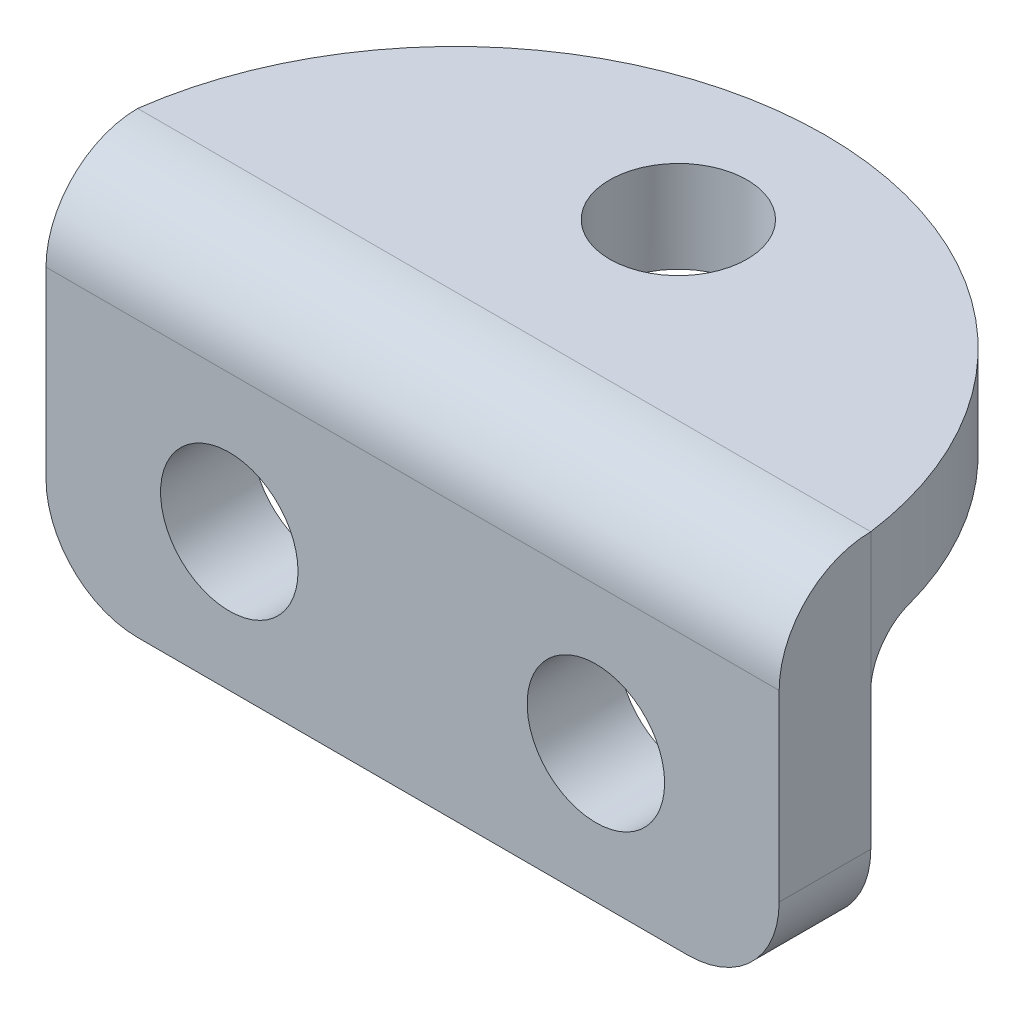
SolidWorks part; units mm, degrees
ref_plane "Front Plane" through (0, 0, 0) normal (0, 0, 1) x (1, 0, 0)
ref_plane "Top Plane" through (0, 0, 0) normal (0, 1, 0) x (1, 0, 0)
ref_plane "Right Plane" through (0, 0, 0) normal (1, 0, 0) x (0, 0, -1)
sketch "Sketch14" plane through (0, 0, 0) normal (1, 0, 0) x (0, 0, -1)
  line L0 (9.4803, -6.1219) -> (9.4803, 1.8781)
  line L1 (9.4803, 1.8781) -> (18.4803, 1.8781)
  line L2 (18.4803, 1.8781) -> (18.4803, -0.1219)
  line L3 (18.4803, -0.1219) -> (11.4803, -0.1219)
  line L4 (11.4803, -0.1219) -> (11.4803, -6.1219)
  line L5 (11.4803, -6.1219) -> (9.4803, -6.1219)
  line L9 (0, -6) -> (0, -4) construction
  line L10 (-2, -4) -> (-2, -6) construction
  line L11 (-2, -6) -> (0, -6) construction
  line L12 (0, -4) -> (0, 2) construction
  line L13 (-2, 0) -> (-2, -4) construction
  line L14 (0, 0) -> (7.0975, 0) construction
  line L15 (0, 0) -> (0, 2) construction
  line L16 (7.0975, 2) -> (0, 2) construction
  line L17 (0, 2) -> (0, 0) construction
  line L18 (0, -6) -> (0, -4)
  line L19 (-2, -4) -> (-2, -6)
  line L20 (-2, -6) -> (0, -6)
  line L21 (0, -4) -> (0, 2)
  line L22 (-2, 0) -> (-2, -4)
  line L23 (0, 0) -> (7.0975, 0)
  line L24 (0, 0) -> (0, 2)
  line L25 (7.0975, 2) -> (0, 2)
  line L26 (0, 2) -> (0, 0)
  arc A0 (0, 2) -> (-2, 0) centre (0, 0) ccw construction
  arc A1 (0, 2) -> (-2, 0) centre (0, 0) ccw
  dimension "D1" = 2
  dimension "D2" = 2
  dimension "D3" = 9
  dimension "D4" = 8
extrude "Boss-Extrude4" add sketch "Sketch14" along normal blind 16 separate body contours L5 L4 L3 L2 L1 L0 region at (0, -2.1219, -9.6007)
sketch "Sketch15" plane through (0, -0.1219, 0) normal (0, -1, 0) x (1, 0, 0)
  line L3 (8, -9.4803) -> (8, -18.4803) construction
  line L4 (16, -9.4803) -> (0, -9.4803) construction
  line L5 (16, -11.4803) -> (0, -11.4803) construction
  line L6 (16, -18.4803) -> (0, -18.4803) construction
  line L11 (0, -11.4803) -> (0, -18.4803)
  line L12 (0, -18.4803) -> (16, -18.4803)
  line L13 (16, -18.4803) -> (16, -11.4803)
  line L14 (16, -11.4803) -> (0, -11.4803)
  line L15 (0, -11.4803) -> (0, -18.4803)
  line L16 (0, -18.4803) -> (16, -18.4803)
  line L17 (16, -18.4803) -> (16, -11.4803)
  line L18 (16, -11.4803) -> (0, -11.4803)
  arc A1 (0, -11.4803) -> (16, -11.4803) centre (8, -10.4089) ccw
  point P10 (8, -18.5246)
  point P11 (0, 0)
  point P14 (8, -18.4803)
  line M7 (0, -11.4803) -> (0, -18.4803)
  line M8 (0, -18.4803) -> (16, -18.4803)
  line M9 (16, -18.4803) -> (16, -11.4803)
  dimension "D1" = 0
extrude "Cut-Extrude3" cut sketch "Sketch15" against normal blind 16 contours A1 M7 M8 | A1 L16 M9 region at (1.8005, -0.1219, -16.7508) region at (14.1995, -0.1219, -16.7508)
sketch "Sketch16" plane through (0, 0, -9.4803) normal (0, 0, 1) x (1, 0, 0)
  line L0 (16, -6.1219) -> (16, 1.8781) construction
  line L1 (0, -6.1219) -> (0, 1.8781) construction
  line L2 (16, -6.1219) -> (0, -6.1219) construction
  circle A0 centre (4, -3.1219) radius 1.5
  circle A1 centre (12, -3.1219) radius 1.5
  dimension "D1" = 3
  dimension "D2" = 4
  dimension "D3" = 4
  dimension "D4" = 3
  dimension "D5" = 3
extrude "Cut-Extrude4" cut sketch "Sketch16" against normal blind 16
fillet "Fillet1" radius 2 2 edges at (16, -6.1219, -10.4803) (0, -6.1219, -10.4803)
fillet "Fillet2" radius 2 1 edges at (8, 1.8781, -9.4803)
sketch "Sketch17" plane through (0, 1.8781, 0) normal (0, 1, 0) x (1, 0, 0)
  line L0 (-0.7049, 15.2803) -> (17.0513, 15.2803) construction
  line L1 (16, 9.4803) -> (0, 9.4803) construction
  line L2 (8, 18.4803) -> (8, 15.2803) construction
  arc A0 (16, 11.4803) -> (0, 11.4803) centre (8, 10.4089) ccw construction
  circle A2 centre (8, 15.2803) radius 1.5
  dimension "D2" = 3
  dimension "D1" = 5.8
extrude "Cut-Extrude5" cut sketch "Sketch17" against normal blind 16
fillet "Fillet3" radius 1 1 edges at (8, -0.1219, -11.4803)
